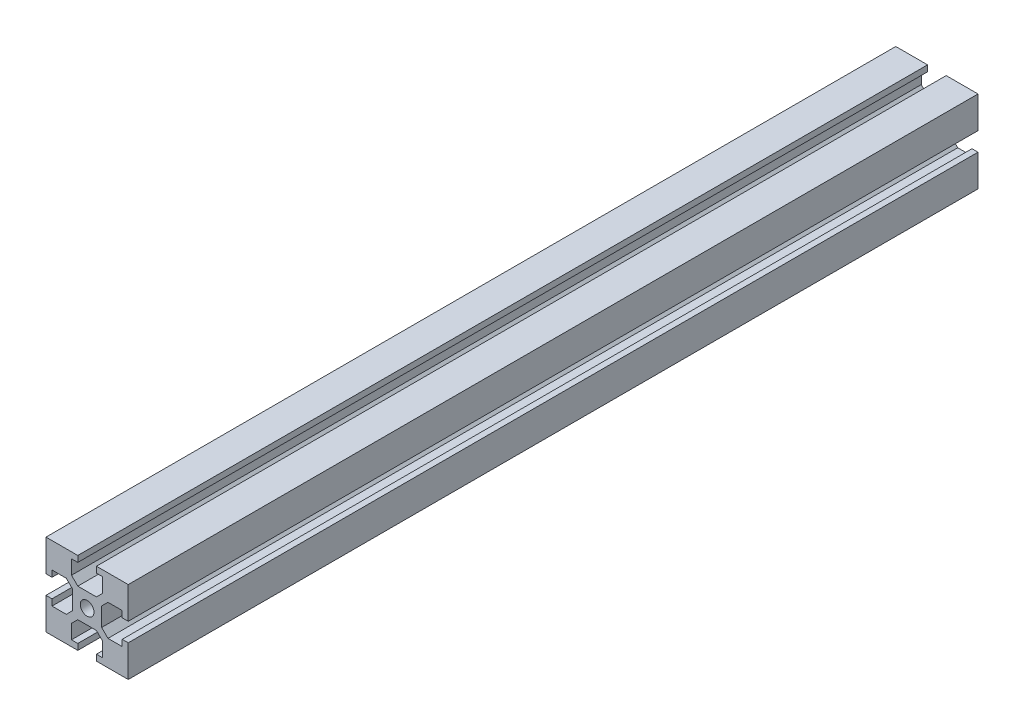
SolidWorks part; units mm, degrees
ref_plane "正面" through (0, 0, 0) normal (0, 0, 1) x (1, 0, 0)
ref_plane "平面" through (0, 0, 0) normal (0, 1, 0) x (1, 0, 0)
ref_plane "右側面" through (0, 0, 0) normal (1, 0, 0) x (0, 0, -1)
sketch "ｽｹｯﾁ2" plane through (0, 0, 0) normal (0, 0, 1) x (1, 0, 0)
  line L0 (0, 0) -> (0, 7.5) construction
  line L1 (-7.5, -7.5) -> (7.5, -7.5) construction
  line L2 (-7.5, -7.5) -> (-7.5, 7.5) construction
  line L3 (-7.5, 7.5) -> (7.5, 7.5) construction
  line L4 (7.5, -7.5) -> (7.5, 7.5) construction
  line L5 (-7.5, -7.5) -> (7.5, 7.5) construction
  line L6 (-7.5, 7.5) -> (7.5, -7.5) construction
  line L8 (1.7, 2.65) -> (-1.7, 2.65)
  line L9 (-2.85, 3.8) -> (2.85, 3.8) construction
  line L10 (-2.85, 6.4) -> (-2.85, 3.8)
  line L11 (2.85, 6.4) -> (2.85, 3.8)
  line L12 (-2.85, 3.8) -> (-1.7, 2.65)
  line L13 (1.7, 2.65) -> (2.85, 3.8)
  line L14 (-2.85, 6.4) -> (-1.7, 6.4)
  line L15 (-1.7, 6.4) -> (-1.7, 7.5)
  line L16 (-1.7, 7.5) -> (-7.5, 7.5)
  line L17 (2.85, 6.4) -> (1.7, 6.4)
  line L18 (1.7, 6.4) -> (1.7, 7.5)
  line L19 (1.7, 7.5) -> (7.5, 7.5)
  line L20 (3.8, 2.85) -> (2.65, 1.7)
  line L21 (2.65, -1.7) -> (2.65, 1.7)
  line L22 (2.65, -1.7) -> (3.8, -2.85)
  line L23 (6.4, -2.85) -> (6.4, -1.7)
  line L24 (6.4, -2.85) -> (3.8, -2.85)
  line L25 (6.4, -1.7) -> (7.5, -1.7)
  line L26 (7.5, -1.7) -> (7.5, -7.5)
  line L27 (6.4, 1.7) -> (7.5, 1.7)
  line L28 (7.5, 1.7) -> (7.5, 7.5)
  line L29 (6.4, 2.85) -> (6.4, 1.7)
  line L30 (6.4, 2.85) -> (3.8, 2.85)
  line L31 (2.85, -3.8) -> (1.7, -2.65)
  line L32 (-1.7, -2.65) -> (1.7, -2.65)
  line L33 (-1.7, -2.65) -> (-2.85, -3.8)
  line L34 (-2.85, -6.4) -> (-1.7, -6.4)
  line L35 (-2.85, -6.4) -> (-2.85, -3.8)
  line L36 (-1.7, -6.4) -> (-1.7, -7.5)
  line L37 (-1.7, -7.5) -> (-7.5, -7.5)
  line L38 (1.7, -6.4) -> (1.7, -7.5)
  line L39 (1.7, -7.5) -> (7.5, -7.5)
  line L40 (2.85, -6.4) -> (1.7, -6.4)
  line L41 (2.85, -6.4) -> (2.85, -3.8)
  line L42 (-3.8, -2.85) -> (-2.65, -1.7)
  line L43 (-2.65, 1.7) -> (-2.65, -1.7)
  line L44 (-2.65, 1.7) -> (-3.8, 2.85)
  line L45 (-6.4, 2.85) -> (-6.4, 1.7)
  line L46 (-6.4, 2.85) -> (-3.8, 2.85)
  line L47 (-6.4, 1.7) -> (-7.5, 1.7)
  line L48 (-7.5, 1.7) -> (-7.5, 7.5)
  line L49 (-6.4, -1.7) -> (-7.5, -1.7)
  line L50 (-7.5, -1.7) -> (-7.5, -7.5)
  line L51 (-6.4, -2.85) -> (-6.4, -1.7)
  line L52 (-6.4, -2.85) -> (-3.8, -2.85)
  circle A0 centre (0, 0) radius 1.25
  point P0 (0, 0)
  point P11 (0, 7.5)
  point P14 (0, 2.65)
  point P17 (0, 3.8)
  dimension "D8" = 2.5
  dimension "D1" = 15
  dimension "D2" = 3.4
  dimension "D3" = 1.1
  dimension "D4" = 2.6
  dimension "D5" = 5.7
  dimension "D6" = 3.4
  dimension "D7" = 4
extrude "ﾎﾞｽ - 押し出し1" add sketch "ｽｹｯﾁ2" along normal blind 155
